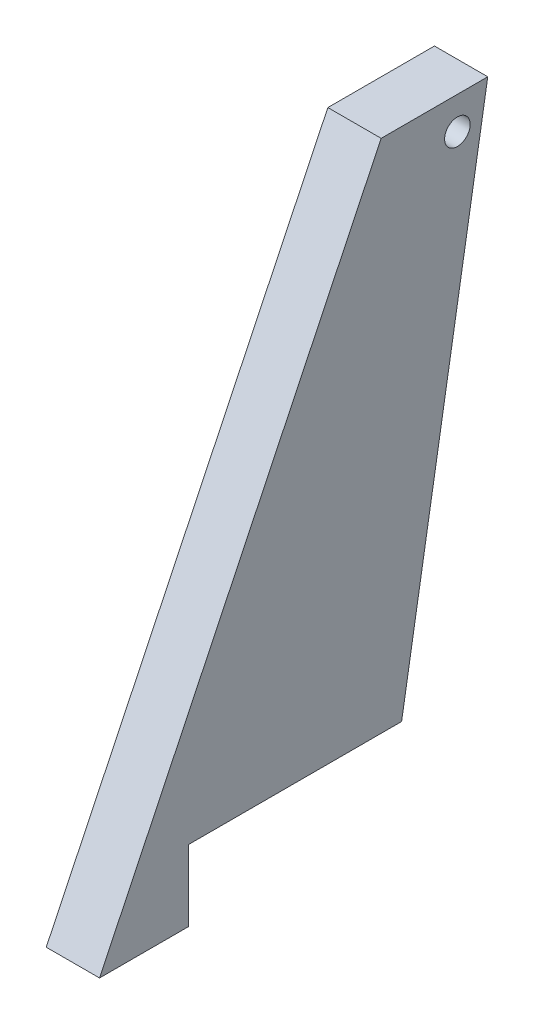
SolidWorks part; units mm, degrees
ref_plane "Front Plane" through (0, 0, 0) normal (0, 0, 1) x (1, 0, 0)
ref_plane "Top Plane" through (0, 0, 0) normal (0, 1, 0) x (1, 0, 0)
ref_plane "Right Plane" through (0, 0, 0) normal (1, 0, 0) x (0, 0, -1)
sketch "Sketch1" plane through (0, 0, 0) normal (1, 0, 0) x (0, 0, -1)
  line L0 (0, 0) -> (-15.875, 0)
  line L4 (0, 12.7) -> (0, 0)
  line L9 (-15.875, 0) -> (34.4445, 104.775)
  line L11 (0, 12.7) -> (38.1, 12.7)
  line L12 (38.1, 12.7) -> (53.4945, 104.775)
  line L13 (53.4945, 104.775) -> (34.4445, 104.775)
  point P3 (37.7073, 105.1207)
  point P6 (54.4336, 106.7305)
  point P7 (41.514, 12.7)
  point P8 (48.5292, 13.0028)
  point P11 (36.2036, 104.9578)
  point P12 (-12.7, 0)
  dimension "D1" = 15.875
  dimension "D2" = 19.05
  dimension "D3" = 64.347
  dimension "D4" = 92.075
  dimension "D5" = 12.7
  dimension "D6" = 38.1
extrude "Boss-Extrude1" add sketch "Sketch1" along normal blind 9.525
sketch "Sketch2" plane through (0, 0, 0) normal (-1, 0, 0) x (0, 0, 1)
  circle A0 centre (-48.0672, 98.9886) radius 2.286
  dimension "D3" = 4.572
  dimension "D1" = 98.9886
  dimension "D2" = 48.0672
extrude "Cut-Extrude1" cut sketch "Sketch2" against normal through all
